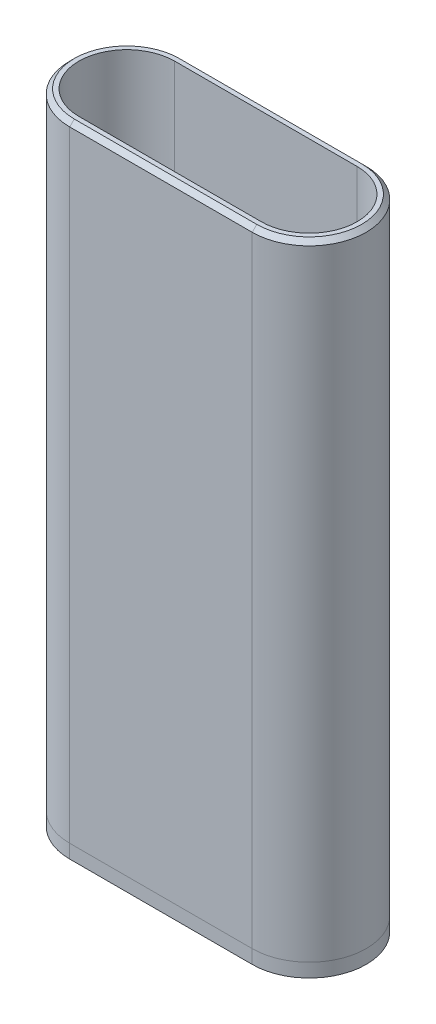
SolidWorks part; units mm, degrees
ref_plane "Front Plane" through (0, 0, 0) normal (0, 0, 1) x (1, 0, 0)
ref_plane "Top Plane" through (0, 0, 0) normal (0, 1, 0) x (1, 0, 0)
ref_plane "Right Plane" through (0, 0, 0) normal (1, 0, 0) x (0, 0, -1)
sketch "Sketch2" plane through (0, 12, 0) normal (0, -1, 0) x (1, 0, 0)
  line L8 (5.45, 3.45) -> (5.45, -3.45) construction
  line L9 (-7.45, -5.65) -> (7.45, -5.65)
  line L10 (-7.45, -5.65) -> (-7.45, 5.65)
  line L11 (-7.45, 5.65) -> (7.45, 5.65)
  line L12 (4.15, -3.65) -> (4.15, 3.65)
  line L13 (4.15, 3.65) -> (-4.15, 3.65)
  line L14 (-4.15, 3.65) -> (-4.15, -3.65)
  line L15 (-4.15, -3.65) -> (4.15, -3.65)
  line L16 (4.15, -3.65) -> (4.15, 3.65)
  line L17 (4.15, 3.65) -> (-4.15, 3.65)
  line L18 (-4.15, 3.65) -> (-4.15, -3.65)
  line L19 (-4.15, -3.65) -> (4.15, -3.65)
  line L20 (7.45, -5.65) -> (7.45, 5.65)
  line L21 (0, 5.65) -> (0, -5.65) construction
  line L22 (-7.45, 0) -> (7.45, 0) construction
  point P0 (0, 0)
  dimension "D2" = 2
  dimension "D3" = 2
  dimension "D4" = 8.3
  dimension "D5" = 7.3
  dimension "D1" = 0.2
extrude "Boss-Extrude1" add sketch "Sketch2" along normal offset from surface (12.6 mm away) 0.6 offset beyond the face yes
sketch "Sketch4" plane through (0, 0, 0) normal (1, 0, 0) x (0, 0, -1)
  line L1 (-1.6, 9.8) -> (-1.6, 8) construction
  line L2 (1.6, 8) -> (1.6, 9.8) construction
  line L3 (2.75, 8) -> (1.6, 8) construction
  line L4 (-1.6, 8) -> (-2.75, 8) construction
  line L5 (-2.75, 8) -> (-2.75, 12) construction
  line L6 (-2.75, 12) -> (-3.45, 12) construction
  line L7 (-3.45, 12) -> (-3.45, 0) construction
  line L8 (-3.45, 0) -> (3.45, 0) construction
  line L9 (3.45, 0) -> (3.45, 12) construction
  line L10 (3.45, 12) -> (2.75, 12) construction
  line L11 (2.75, 12) -> (2.75, 8) construction
  line L13 (-1.6, 9.8) -> (-1.6, 8) construction
  line L14 (1.6, 8) -> (1.6, 9.8) construction
  line L15 (2.75, 8) -> (1.6, 8) construction
  line L16 (-1.6, 8) -> (-2.75, 8) construction
  line L17 (-2.75, 8) -> (-2.75, 12) construction
  line L18 (-2.75, 12) -> (-3.45, 12) construction
  line L19 (-3.45, 12) -> (-3.45, 0) construction
  line L20 (-3.45, 0) -> (3.45, 0) construction
  line L21 (3.45, 0) -> (3.45, 12) construction
  line L22 (3.45, 12) -> (2.75, 12) construction
  line L23 (2.75, 12) -> (2.75, 8) construction
  line L24 (0, -990) -> (0, 49010) construction
  line L25 (-2.3, 10.1) -> (2.3, 10.1)
  line L26 (-2.3, 10.1) -> (-2.3, 7)
  line L27 (-2.3, 7) -> (2.3, 7)
  line L28 (1.6, 10) -> (-1.6, 10)
  line L29 (-1.6, 10) -> (-1.6, 9.8)
  line L30 (-1.6, 9.8) -> (1.6, 9.8)
  line L31 (1.6, 9.8) -> (1.6, 10)
  line L32 (1.6, 10) -> (-1.6, 10) construction
  line L33 (-1.6, 10) -> (-1.6, 9.8) construction
  line L34 (2.3, 10.1) -> (2.3, 7)
  line L35 (1.6, 9.8) -> (1.6, 10) construction
  point P20 (0, 10)
  dimension "D2" = 0.7
  dimension "D3" = 0.1
  dimension "D4" = 1
  dimension "D1" = 0
extrude "Cut-Extrude1" cut sketch "Sketch4" against normal through all both and the other way through all
sketch "Sketch5" plane through (0, -0.6, 0) normal (0, -1, 0) x (1, 0, 0)
  line L0 (-20, 0) -> (20, 0) construction
  line L1 (-20, 12.5) -> (20, 12.5)
  line L2 (-20, -12.5) -> (20, -12.5)
  arc A0 (-20, 12.5) -> (-20, -12.5) centre (-20, 0) ccw
  arc A1 (20, -12.5) -> (20, 12.5) centre (20, 0) ccw
  point P2 (0, 0)
  dimension "D1" = 25
  dimension "D2" = 40
extrude "Boss-Extrude2" add sketch "Sketch5" along normal blind 3
sketch "Sketch7" plane through (0, -0.6, 0) normal (0, 1, 0) x (1, 0, 0)
  line L0 (-20, -10.5) -> (20, -10.5)
  line L1 (20, 10.5) -> (-20, 10.5)
  line L2 (-20, -12.5) -> (20, -12.5)
  line L3 (20, 12.5) -> (-20, 12.5)
  line L4 (-20, -12.5) -> (20, -12.5)
  line L5 (20, 12.5) -> (-20, 12.5)
  arc A0 (20, -10.5) -> (20, 10.5) centre (20, 0) ccw
  arc A1 (-20, 10.5) -> (-20, -10.5) centre (-20, 0) ccw
  arc A2 (-20, 12.5) -> (-20, -12.5) centre (-20, 0) ccw
  arc A3 (20, -12.5) -> (20, 12.5) centre (20, 0) ccw
  arc A4 (-20, 12.5) -> (-20, -12.5) centre (-20, 0) ccw
  arc A5 (20, -12.5) -> (20, 12.5) centre (20, 0) ccw
  dimension "D1" = 0
  dimension "D2" = 2
extrude "Boss-Extrude3" add sketch "Sketch7" along normal blind 137 separate body
sketch "Sketch8" plane through (0, -0.6, 0) normal (0, -1, 0) x (1, 0, 0)
  line L0 (-7.45, -5.65) -> (7.45, -5.65) construction
  line L1 (-7.45, 5.65) -> (-7.45, -5.65) construction
  line L2 (7.45, 5.65) -> (-7.45, 5.65) construction
  line L3 (7.45, -5.65) -> (7.45, 5.65) construction
  line L4 (-7.45, -5.65) -> (7.45, -5.65) construction
  line L5 (-7.45, 5.65) -> (-7.45, -5.65) construction
  line L6 (7.45, 5.65) -> (-7.45, 5.65) construction
  line L7 (7.45, -5.65) -> (7.45, 5.65) construction
  line L12 (20, -12.5) -> (-20, -12.5) construction
  line L13 (-20, 12.5) -> (20, 12.5) construction
  line L14 (20, -12.5) -> (-20, -12.5)
  line L15 (-20, 12.5) -> (20, 12.5)
  line L17 (-14.45, 7.65) -> (14.45, 7.65)
  line L18 (-14.45, 7.65) -> (-14.45, -7.65)
  line L19 (-14.45, -7.65) -> (14.45, -7.65)
  line L20 (14.45, 7.65) -> (14.45, -7.65)
  arc A0 (20, -12.5) -> (20, 12.5) centre (20, 0) ccw construction
  arc A1 (-20, 12.5) -> (-20, -12.5) centre (-20, 0) ccw construction
  arc A2 (20, -12.5) -> (20, 12.5) centre (20, 0) ccw
  arc A3 (-20, 12.5) -> (-20, -12.5) centre (-20, 0) ccw
  dimension "D1" = 2
  dimension "D2" = 2
  dimension "D3" = 7
  dimension "D4" = 7
extrude "Boss-Extrude4" add sketch "Sketch8" against normal blind 7.2
sketch "Sketch9" plane through (0, -0.6, 0) normal (0, -1, 0) x (1, 0, 0)
  line L0 (-20, 0) -> (20, 0) construction
  point P4 (0, 0)
  dimension "D1" = 40
hole_wizard "M3 Clearance Hole1" positions "Sketch10" profile "Sketch11" hole size "M3" standard "ANSI Metric" end condition through all
sketch "Sketch10" plane through (0, -0.6, 0) normal (0, -1, 0) x (-1, 0, 0)
  point P0 (20, 0)
  point P3 (-20, 0)
sketch "Sketch11" plane through (-20, -0.6, 0) normal (1, 0, 0) x (0, 0, -1)
  line L0 (0, 0) -> (0, 137)
  line L1 (0, 137) -> (1.8, 137)
  line L2 (1.8, 137) -> (1.8, 0)
  line L5 (1.8, 0) -> (0, 0)
  line L11 (0, -6.35) -> (0, 107.95) construction
  dimension "Thru Hole Dia." = 3.6
  dimension "Thru Hole Depth" = 137
ref_plane "Plane1" through (0, 2.4, 0) normal (0, 1, 0) x (1, 0, 0)
sketch "Sketch13" plane through (0, 2.4, 0) normal (0, 1, 0) x (1, 0, 0)
  line L0 (-18.3257, 2.9) -> (-14.45, 2.9)
  line L1 (-18.3257, 2.9) -> (-21.6743, 2.9)
  line L2 (-21.6743, 2.9) -> (-23.3486, 0)
  line L3 (-23.3486, 0) -> (-21.6743, -2.9)
  line L4 (-21.6743, -2.9) -> (-18.3257, -2.9)
  line L5 (-18.3257, -2.9) -> (-16.6514, 0)
  line L6 (-16.6514, 0) -> (-18.3257, 2.9)
  line L13 (-14.45, -7.65) -> (-14.45, 7.65) construction
  line L14 (-14.45, 2.9) -> (-14.45, -2.9)
  line L15 (-14.45, -2.9) -> (-18.3257, -2.9)
  circle A0 centre (-20, 0) radius 2.9 construction
  dimension "D1" = 5.8
extrude "Cut-Extrude2" cut sketch "Sketch13" along normal blind 3 contours L15 L14 L0 L6 L5 | L5 L6 L1 L2 L3 L4 region at (-20, 2.4, 0) region at (-16.0077, 2.4, 0)
chamfer "Chamfer1" distance 1 angle 45 4 edges at (32.5, 136.4, 0) (0, 136.4, -12.5) (0, 136.4, 12.5) (-32.5, 136.4, 0)
mirror "Mirror1" about plane through (0, 0, 0) normal (1, 0, 0) of "Cut-Extrude2"
chamfer "Chamfer2" distance 2 angle 45 4 edges at (-14.45, -0.6, 0) (0, -0.6, 7.65) (14.45, -0.6, 0) (0, -0.6, -7.65)
equation "\"case_length\"= 140"
equation "\"plate_thickness\"= 3"
equation "\"D1@Boss-Extrude2\"=\"plate_thickness\""
equation "\"D1@Boss-Extrude3\"=\"case_length\"-\"plate_thickness\""
equation "\"case_height\"= 25"
equation "\"case_width\"= 65"
equation "\"case_to_shell_offset\"= 19.6"
equation "\"body_tip_distance\"= 30"
equation "\"D2@Sketch5\"=\"case_width\"-\"case_height\""
equation "\"D1@Sketch5\"=\"case_height\""
equation "\"D1@Sketch9\"= \"case_width\" - \"case_height\""
equation "\"D2@Sketch8\"=\"D1@Sketch8\""
equation "\"D4@Sketch8\"=\"D3@Sketch8\""
